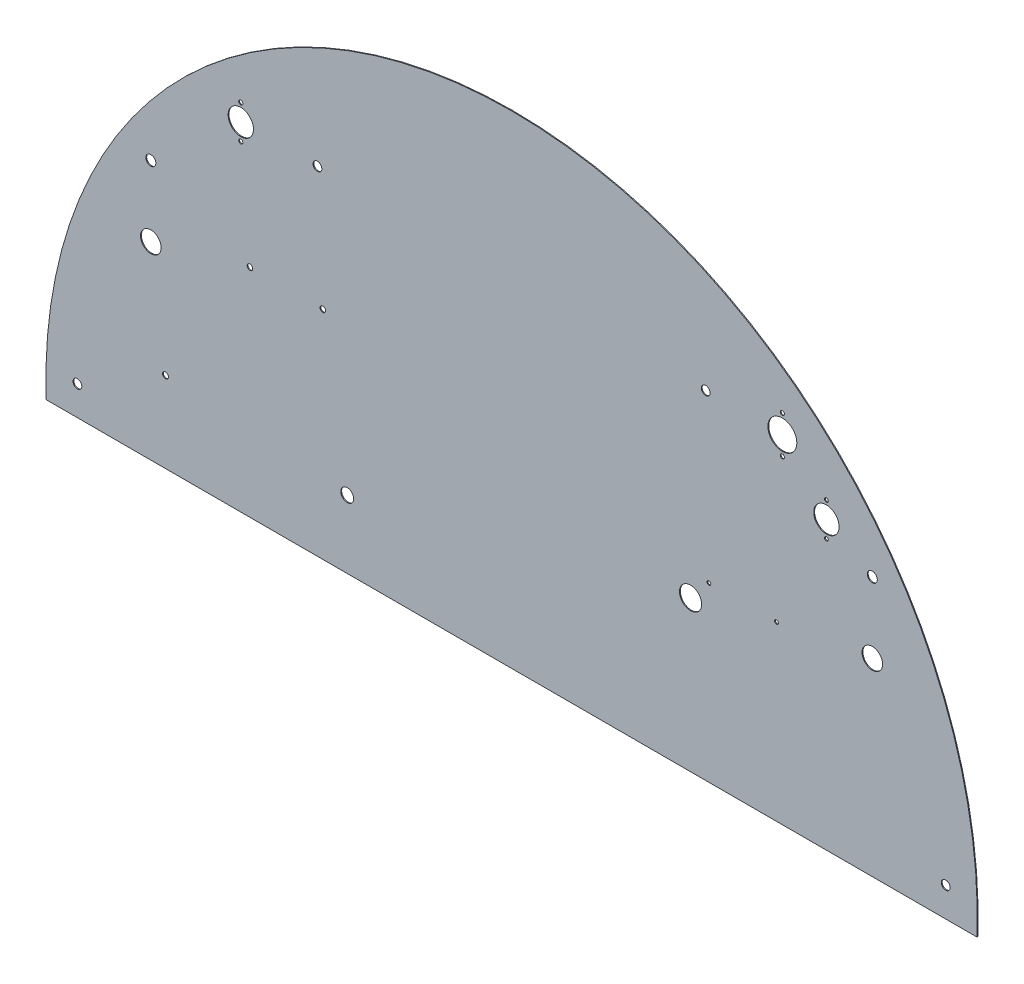
SolidWorks part; units mm, degrees
ref_plane "Front Plane" through (0, 0, 0) normal (0, 0, 1) x (1, 0, 0)
ref_plane "Top Plane" through (0, 0, 0) normal (0, 1, 0) x (1, 0, 0)
ref_plane "Right Plane" through (0, 0, 0) normal (1, 0, 0) x (0, 0, -1)
sketch "Base Sketch" plane through (0, 0, 0) normal (0, 0, 1) x (1, 0, 0)
  line L0 (0, 0) -> (750.8875, 0) construction
  line L1 (375.4437, 0) -> (375.4437, 266.7) construction
  line L2 (543.3219, 266.7) -> (207.5656, 266.7) construction
  line L3 (-26.9875, -25.4) -> (777.875, -25.4)
  line L4 (375.4437, 0) -> (375.4437, -25.4) construction
  line L5 (375.4437, 266.7) -> (375.4437, 355.6) construction
  line L7 (-1.5875, -25.4) -> (375.4437, -25.4) construction
  line L8 (-1.5875, -25.4) -> (-1.5875, 127) construction
  line L9 (-1.5875, 127) -> (375.4437, 127) construction
  line L10 (375.4437, -25.4) -> (375.4437, 127) construction
  line L11 (23.8125, -25.4) -> (375.4437, -25.4) construction
  line L12 (23.8125, -25.4) -> (23.8125, 177.8) construction
  line L13 (23.8125, 177.8) -> (375.4437, 177.8) construction
  line L14 (375.4437, -25.4) -> (375.4437, 177.8) construction
  line L15 (49.2125, -25.4) -> (375.4437, -25.4) construction
  line L16 (49.2125, -25.4) -> (49.2125, 215.9) construction
  line L17 (49.2125, 215.9) -> (375.4437, 215.9) construction
  line L18 (375.4437, -25.4) -> (375.4437, 215.9) construction
  line L19 (74.6125, -25.4) -> (375.4437, -25.4) construction
  line L20 (74.6125, -25.4) -> (74.6125, 257.175) construction
  line L21 (74.6125, 257.175) -> (375.4437, 257.175) construction
  line L22 (375.4437, -25.4) -> (375.4437, 257.175) construction
  line L23 (100.0125, -25.4) -> (375.4437, -25.4) construction
  line L24 (100.0125, -25.4) -> (100.0125, 273.05) construction
  line L25 (100.0125, 273.05) -> (375.4437, 273.05) construction
  line L26 (375.4437, -25.4) -> (375.4437, 273.05) construction
  line L27 (125.4125, -25.4) -> (375.4437, -25.4) construction
  line L28 (125.4125, -25.4) -> (125.4125, 292.1) construction
  line L29 (125.4125, 292.1) -> (375.4437, 292.1) construction
  line L30 (375.4437, -25.4) -> (375.4437, 292.1) construction
  line L31 (150.8125, -25.4) -> (375.4437, -25.4) construction
  line L32 (150.8125, -25.4) -> (150.8125, 301.625) construction
  line L33 (150.8125, 301.625) -> (375.4437, 301.625) construction
  line L34 (375.4437, -25.4) -> (375.4437, 301.625) construction
  line L35 (176.2125, -25.4) -> (375.4437, -25.4) construction
  line L36 (176.2125, -25.4) -> (176.2125, 314.325) construction
  line L37 (176.2125, 314.325) -> (375.4437, 314.325) construction
  line L38 (375.4437, -25.4) -> (375.4437, 314.325) construction
  line L39 (201.6125, -25.4) -> (375.4437, -25.4) construction
  line L40 (201.6125, -25.4) -> (201.6125, 322.2625) construction
  line L41 (201.6125, 322.2625) -> (375.4437, 322.2625) construction
  line L42 (375.4437, -25.4) -> (375.4437, 322.2625) construction
  line L43 (227.0125, -25.4) -> (375.4437, -25.4) construction
  line L44 (227.0125, -25.4) -> (227.0125, 330.2) construction
  line L45 (227.0125, 330.2) -> (375.4437, 330.2) construction
  line L46 (375.4437, -25.4) -> (375.4437, 330.2) construction
  line L47 (252.4125, -25.4) -> (375.4437, -25.4) construction
  line L48 (252.4125, -25.4) -> (252.4125, 338.1375) construction
  line L49 (252.4125, 338.1375) -> (375.4437, 338.1375) construction
  line L50 (375.4437, -25.4) -> (375.4437, 338.1375) construction
  line L51 (277.8125, -25.4) -> (375.4437, -25.4) construction
  line L52 (277.8125, -25.4) -> (277.8125, 346.075) construction
  line L53 (277.8125, 346.075) -> (375.4437, 346.075) construction
  line L54 (375.4437, -25.4) -> (375.4437, 346.075) construction
  circle A0 centre (0, 0) radius 3.81
  circle A1 centre (750.8875, 0) radius 3.81
  circle A2 centre (207.5656, 266.7) radius 3.81
  circle A3 centre (543.3219, 266.7) radius 3.81
  arc A4 (-26.9875, -25.4) -> (777.875, -25.4) centre (375.4437, -47.434) cw construction
  arc A7 (-26.9875, -25.4) -> (777.875, -25.4) centre (375.4437, -10.5417) cw
  point P9 (375.4437, 266.7)
  point P55 (0, 0)
  dimension "D1" = 7.62
  dimension "D2" = 750.8875
  dimension "D3" = 266.7
  dimension "D4" = 335.7562
  dimension "D5" = 25.4
  dimension "D6" = 26.9875
  dimension "D7" = 381
  dimension "D8" = 25.4
  dimension "D9" = 152.4
  dimension "D10" = 50.8
  dimension "D11" = 203.2
  dimension "D12" = 76.2
  dimension "D13" = 241.3
  dimension "D14" = 101.6
  dimension "D15" = 282.575
  dimension "D16" = 127
  dimension "D17" = 298.45
  dimension "D18" = 152.4
  dimension "D19" = 317.5
  dimension "D20" = 177.8
  dimension "D21" = 327.025
  dimension "D22" = 203.2
  dimension "D23" = 339.725
  dimension "D24" = 228.6
  dimension "D25" = 347.6625
  dimension "D26" = 254
  dimension "D27" = 355.6
  dimension "D28" = 279.4
  dimension "D29" = 363.5375
  dimension "D30" = 304.8
  dimension "D31" = 371.475
extrude "Base w Mount Holes" add sketch "Base Sketch" along normal blind 0.7366 contours A7 L3 A3 A2 A1 A0 region at (375.4438, 152.3844, 0)
sketch "Throttle and Choke Cutout Sketch" plane through (0, 0, 0.7366) normal (0, 0, 1) x (1, 0, 0)
  line L0 (375.4437, 392.1637) -> (375.4438, -25.4) construction
  line L1 (-26.9875, -25.4) -> (777.875, -25.4) construction
  line L2 (63.5, 199.0725) -> (63.5, 138.1125) construction
  arc A0 (777.875, -25.4) -> (-26.9875, -25.4) centre (375.4437, -10.5417) ccw construction
  circle A1 centre (63.5, 138.1125) radius 8.89
  circle A2 centre (63.5, 199.0725) radius 4.318
  circle A3 centre (687.3875, 138.1125) radius 8.89
  circle A4 centre (687.3875, 199.0725) radius 4.318
  point P11 (0, 0)
  dimension "D1" = 17.78
  dimension "D2" = 8.636
  dimension "D3" = 63.5
  dimension "D4" = 138.1125
  dimension "D5" = 199.0725
extrude "Throttle and Choke Cutouts" cut sketch "Throttle and Choke Cutout Sketch" against normal through all
sketch "Starter Relay Mount Sketch" plane through (0, 0, 0.7366) normal (0, 0, 1) x (1, 0, 0)
  line L0 (149.225, 161.925) -> (212.217, 161.925) construction
  circle A0 centre (149.225, 161.925) radius 2.3813
  circle A1 centre (212.217, 161.925) radius 2.3813
  dimension "D2" = 4.7625
  dimension "D1" = 62.992
  dimension "D3" = 149.225
  dimension "D4" = 161.925
extrude "Starter Relay Mount" cut sketch "Starter Relay Mount Sketch" against normal through all
sketch "Oil Pressure Sender Clamp Mount Sketch" plane through (0, 0, 0.7366) normal (0, 0, 1) x (1, 0, 0)
  circle A0 centre (76.2, 44.45) radius 2.54
  dimension "D1" = 5.08
  dimension "D2" = 76.2
  dimension "D3" = 44.45
extrude "Oil Pressure Sender Clamp Mount" cut sketch "Oil Pressure Sender Clamp Mount Sketch" against normal through all contours A0
sketch "Starter Power Cutout Sketch" plane through (0, 0, 0.7366) normal (0, 0, 1) x (1, 0, 0)
  circle A0 centre (233.3625, 33.3375) radius 5.588
  dimension "D1" = 11.176
  dimension "D2" = 233.3625
  dimension "D3" = 33.3375
extrude "Starter Power Cutout" cut sketch "Starter Power Cutout Sketch" against normal through all
sketch "Fuel Return Cutout Sketch" plane through (0, 0, 0.7366) normal (0, 0, 1) x (1, 0, 0)
  circle A0 centre (530.225, 104.775) radius 9.5758
  dimension "D3" = 19.1516
  dimension "D1" = 530.225
  dimension "D2" = 104.775
extrude "Fuel Return Cutout" cut sketch "Fuel Return Cutout Sketch" against normal through all
sketch "Brake Master Cyl Mount Sketch" plane through (0, 0, 0.7366) normal (0, 0, 1) x (1, 0, 0)
  line L0 (546.1, 123.825) -> (604.52, 123.825) construction
  circle A0 centre (546.1, 123.825) radius 1.6256
  circle A1 centre (604.52, 123.825) radius 1.6256
  dimension "D1" = 3.2512
  dimension "D2" = 546.1
  dimension "D3" = 123.825
  dimension "D4" = 58.42
extrude "Brake Master Cyl Mount" cut sketch "Brake Master Cyl Mount Sketch" against normal through all
sketch "Cutout - AS012 - Instrumentation Right Sketch" plane through (0, 0, 0.7366) normal (0, 0, 1) x (1, 0, 0)
  line L0 (141.2875, 252.1496) -> (141.2875, 266.7) construction
  line L1 (141.2875, 266.7) -> (141.2875, 281.2504) construction
  circle A0 centre (141.2875, 266.7) radius 10.9499
  circle A1 centre (141.2875, 252.1496) radius 1.8034
  circle A2 centre (141.2875, 281.2504) radius 1.8034
  point P6 (0, 0)
  point P7 (0, 0)
  dimension "D1" = 21.8999
  dimension "D2" = 3.6068
  dimension "D3" = 29.1008
  dimension "D4" = 141.2875
  dimension "D5" = 266.7
extrude "Cutout - AS012 - Instrumentation Right" cut sketch "Cutout - AS012 - Instrumentation Right Sketch" against normal through all
sketch "Cutout - AS014 - Tach and CDI Enables Left Sketch" plane through (0, 0, 0.7366) normal (0, 0, 1) x (1, 0, 0)
  line L0 (609.6, 250.4504) -> (609.6, 266.7) construction
  line L1 (609.6, 266.7) -> (609.6, 282.9497) construction
  line L2 (609.6, 266.7) -> (543.3219, 266.7) construction
  circle A0 centre (609.6, 266.7) radius 12.4968
  circle A1 centre (609.6, 282.9497) radius 1.8034
  circle A2 centre (609.6, 250.4504) radius 1.8034
  dimension "D2" = 3.6068
  dimension "D3" = 24.9936
  dimension "D1" = 32.4993
  dimension "D4" = 609.6
extrude "Cutout - AS014 - Tach and CDI Enables Left" cut sketch "Cutout - AS014 - Tach and CDI Enables Left Sketch" against normal through all
sketch "Cutout - AS012 - Instrumentation Left Sketch" plane through (0, 0, 0.7366) normal (0, 0, 1) x (1, 0, 0)
  line L0 (647.7, 207.6996) -> (647.7, 222.25) construction
  line L1 (647.7, 222.25) -> (647.7, 236.8004) construction
  circle A0 centre (647.7, 222.25) radius 10.9499
  circle A1 centre (647.7, 236.8004) radius 1.6002
  circle A2 centre (647.7, 207.6996) radius 1.6002
  point P6 (0, 0)
  dimension "D1" = 21.8999
  dimension "D2" = 3.2004
  dimension "D3" = 29.1008
  dimension "D4" = 647.7
  dimension "D5" = 222.25
extrude "Cutout - AS012 - Instrumentation Left" cut sketch "Cutout - AS012 - Instrumentation Left Sketch" against normal through all
